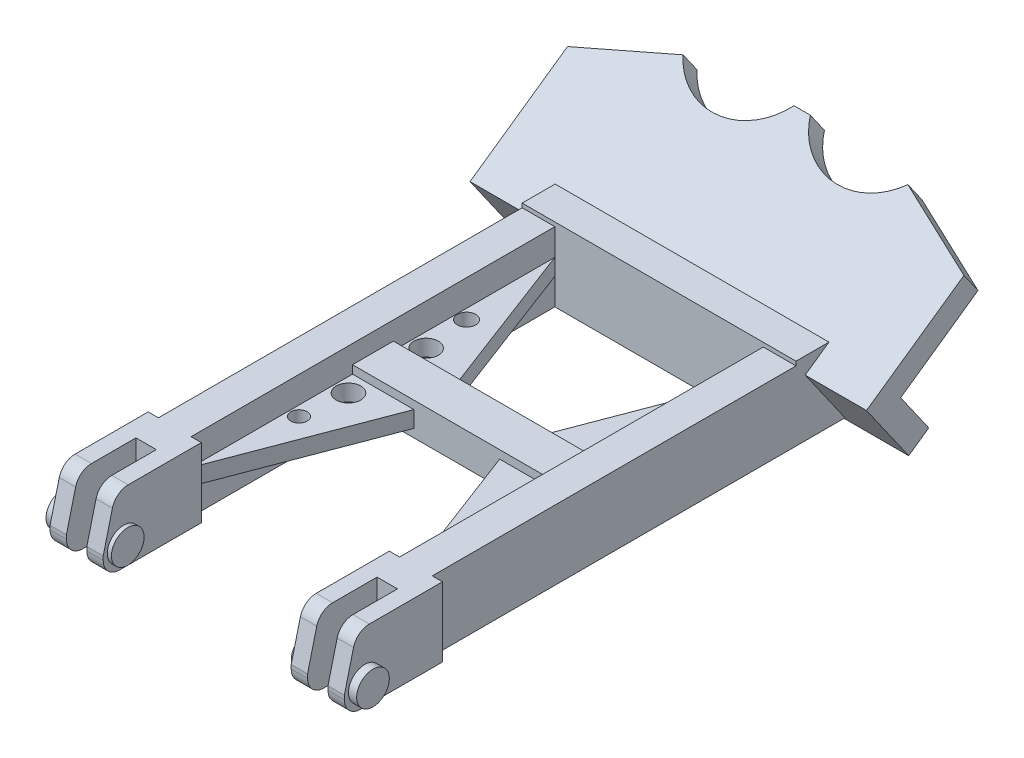
SolidWorks part; units mm, degrees
ref_plane "Front Plane" through (0, 0, 0) normal (0, 0, 1) x (1, 0, 0)
ref_plane "Top Plane" through (0, 0, 0) normal (0, 1, 0) x (1, 0, 0)
ref_plane "Right Plane" through (0, 0, 0) normal (1, 0, 0) x (0, 0, -1)
sketch "Sketch1" plane through (0, 0, 0) normal (0, 1, 0) x (1, 0, 0)
  line L0 (0, 0) -> (0, 8.9) construction
  line L1 (-3.35, 0) -> (-2.55, 0) construction
  line L2 (-3.35, 0) -> (-3.35, 10.1)
  line L3 (-3.35, 10.1) -> (3.35, 10.1)
  line L4 (3.35, 0) -> (3.35, 10.1)
  line L5 (-3.35, 0) -> (-3.6, 0)
  line L6 (-3.6, 0) -> (-3.6, -2.4)
  line L7 (-3.6, -2.4) -> (-2.3, -2.4)
  line L8 (2.55, 0) -> (3.35, 0) construction
  line L9 (-2.55, 0) -> (-2.55, 8.9)
  line L10 (2.55, 0) -> (2.55, 8.9)
  line L11 (-2.55, 8.9) -> (2.55, 8.9)
  line L12 (-2.3, -2.4) -> (-2.3, 0)
  line L13 (-2.3, 0) -> (-2.55, 0)
  line L14 (2.55, 0) -> (2.3, 0)
  line L15 (2.3, 0) -> (2.3, -2.4)
  line L16 (2.3, -2.4) -> (3.6, -2.4)
  line L17 (3.6, -2.4) -> (3.6, 0)
  line L18 (3.6, 0) -> (3.35, 0)
  dimension "D1" = 1.2
  dimension "D2" = 6.7
  dimension "D3" = 0.8
  dimension "D4" = 0.8
  dimension "D5" = 0.25
  dimension "D6" = 2.4
  dimension "D7" = 12.5
extrude "Boss-Extrude1" add sketch "Sketch1" along normal mid plane 1.7
sketch "Sketch3" plane through (0, 0, 0) normal (0, 1, 0) x (1, 0, 0)
  line L0 (-1.05, 3.95) -> (-2.55, 3.95) construction
  line L2 (-2.55, 3.95) -> (-2.55, 0)
  line L3 (-2.55, 0) -> (-2.55, 8.9) construction
  line L4 (-2.55, 0) -> (-1.05, 3.95)
  line L7 (0, 0) -> (0, 13.4734) construction
  line L8 (2.55, 0) -> (1.05, 3.95)
  line L9 (2.55, 3.95) -> (2.55, 0)
  line L10 (1.05, 3.95) -> (2.55, 3.95) construction
  line L11 (-2.55, 4.45) -> (2.55, 4.45) construction
  line L12 (2.55, 8.9) -> (2.55, 0) construction
  line L13 (-1.05, 3.95) -> (1.05, 3.95)
  line L14 (1.05, 4.95) -> (2.55, 4.95) construction
  line L15 (-1.05, 4.95) -> (-2.55, 4.95) construction
  line L16 (-1.05, 4.95) -> (1.05, 4.95)
  line L17 (2.55, 4.95) -> (2.55, 8.9)
  line L18 (2.55, 8.9) -> (1.05, 4.95)
  line L19 (-2.55, 8.9) -> (-1.05, 4.95)
  line L20 (-2.55, 4.95) -> (-2.55, 8.9)
  line L21 (2.55, 4.95) -> (2.55, 3.95)
  line L22 (-2.55, 4.95) -> (-2.55, 3.95)
  line L23 (-2.2, 5.4) -> (-2.31, 6.5) construction
  line L24 (-2.2, 3.5) -> (-2.31, 2.4) construction
  circle A0 centre (-2.2, 3.5) radius 0.3
  circle A1 centre (2.2, 3.5) radius 0.3
  circle A2 centre (-2.31, 2.4) radius 0.2
  circle A3 centre (-2.31, 6.5) radius 0.225
  circle A4 centre (2.2, 5.4) radius 0.3
  circle A5 centre (-2.2, 5.4) radius 0.3
  circle A7 centre (2.31, 2.4) radius 0.2
  circle A9 centre (2.31, 6.5) radius 0.225
  dimension "D1" = 0.6
  dimension "D6" = 0.4
  dimension "D9" = 0.45
  dimension "D2" = 1
  dimension "D3" = 0.35
  dimension "D4" = 2.1
  dimension "D5" = 0.45
  dimension "D7" = 1.1
  dimension "D10" = 1.1
extrude "Boss-Extrude2" add sketch "Sketch3" along normal mid plane 0.4
fillet "Fillet1" radius 0.4 2 edges at (2.95, -0.85, 2.4) (-2.95, -0.85, 2.4)
chamfer "Chamfer1" distance 1.2 distance2 0.3 2 edges at (2.95, 0.85, 2.4) (-2.95, 0.85, 2.4) first distance on face at (2.95, 0.2, 2.4) first distance on face at (-2.95, 0.2, 2.4)
fillet "Fillet2" radius 0.4 2 edges at (2.95, 0.85, 2.1) (-2.95, 0.85, 2.1)
sketch "Sketch7" plane through (-3.6, 0, 0) normal (-1, 0, 0) x (0, 0, 1)
  line L0 (2.4, -0.35) -> (2.4, -0.45) construction
  line L2 (0, -0.85) -> (2, -0.85) construction
  circle A0 centre (1.9, -0.35) radius 0.5 construction
  circle A1 centre (1.9, -0.35) radius 0.4
  dimension "D1" = 1
  dimension "D2" = 0.8
extrude "Boss-Extrude4" add sketch "Sketch7" along normal blind 0.2 and the other way blind 1.4
sketch "Sketch8" plane through (3.6, 0, 0) normal (1, 0, 0) x (0, 0, -1)
  circle A1 centre (-1.9, -0.35) radius 0.4
  circle A2 centre (-1.9, -0.35) radius 0.4
  dimension "D1" = 0
extrude "Boss-Extrude5" add sketch "Sketch8" along normal blind 0.2 and the other way blind 1.4
sketch "Sketch6" plane through (0, 0.85, 0) normal (0, 1, 0) x (1, 0, 0)
  line L0 (-2.3, -2.4) -> (-3.6, -2.4) construction
  line L1 (-3.2, -0.7) -> (-2.7, -0.7)
  line L2 (-3.2, -0.7) -> (-3.2, -2.4)
  line L3 (-3.2, -2.4) -> (-2.7, -2.4)
  line L4 (-2.7, -0.7) -> (-2.7, -2.4)
  line L6 (2.7, -0.7) -> (2.7, -2.4)
  line L7 (3.2, -2.4) -> (2.7, -2.4)
  line L8 (3.2, -0.7) -> (3.2, -2.4)
  line L9 (3.2, -0.7) -> (2.7, -0.7)
  line L10 (-3.35, 0) -> (-3.6, 0) construction
  line L11 (-3.6, 0) -> (-3.6, -1.7877) construction
  line L12 (-2.3, -1.7877) -> (-2.3, 0) construction
  line L13 (0, 0) -> (0, 1.2086) construction
  dimension "D1" = 0.7
  dimension "D2" = 0.4
  dimension "D3" = 0.4
extrude "Cut-Extrude1" cut sketch "Sketch6" against normal through all
sketch "Sketch11" plane through (0, 0.2, 0) normal (0, 1, 0) x (1, 0, 0)
  line L0 (-2.55, 0) -> (-2.55, 8.9) construction
  line L1 (-2.55, 4.95) -> (2.55, 4.95)
  line L2 (-2.55, 4.95) -> (-2.55, 3.95)
  line L3 (-2.55, 3.95) -> (2.55, 3.95)
  line L4 (2.55, 4.95) -> (2.55, 3.95)
  line L5 (2.55, 8.9) -> (2.55, 0) construction
  line L6 (1.05, 4.95) -> (-1.05, 4.95) construction
  line L7 (-1.05, 3.95) -> (1.05, 3.95) construction
extrude "Boss-Extrude8" add sketch "Sketch11" along normal blind 0.2 and the other way blind 0.6
sketch "Sketch12" plane through (0, 0, 0) normal (1, 0, 0) x (0, 0, -1)
  line L0 (9.1249, 0.5426) -> (10.1574, -0.9319)
  line L1 (9.1249, 0.5426) -> (12.4015, 2.8369)
  line L2 (10.1574, -0.9319) -> (10.6488, -0.5878)
  line L3 (10.6488, -0.5878) -> (9.9606, 0.3952)
  line L4 (9.9606, 0.3952) -> (12.7457, 2.3454)
  line L5 (12.7457, 2.3454) -> (12.4015, 2.8369)
  line L6 (0, -0.85) -> (10.1, -0.85) construction
  dimension "D1" = 55
  dimension "D2" = 0.6
  dimension "D3" = 0.6
  dimension "D4" = 4
  dimension "D5" = 1.8
  dimension "D6" = 0.1
extrude "Boss-Extrude9" add sketch "Sketch12" along normal mid plane 9.7
sketch "Sketch13" plane through (3.35, 0, 0) normal (1, 0, 0) x (0, 0, -1)
  line L3 (9.9606, 0.3952) -> (10.1, 0.1961)
  line L4 (10.1, 0.1961) -> (10.1, 0.4929)
  line L5 (10.1, 0.4929) -> (9.9606, 0.3952)
  line L6 (9.9606, 0.3952) -> (10.1, 0.1961)
  line L7 (10.1, 0.1961) -> (10.1, 0.4929)
  line L8 (10.1, 0.4929) -> (9.9606, 0.3952)
  dimension "D1" = 0
extrude "Cut-Extrude2" cut sketch "Sketch13" against normal blind 9.7
sketch "Sketch16" plane through (0, 0, 0) normal (-1, 0, 0) x (0, 0, 1)
  line L0 (-9.9606, 0.3952) -> (-12.7457, 2.3454) construction
  line L1 (-10.6488, -0.5878) -> (-9.9606, 0.3952) construction
  line L2 (-9.9606, 0.3952) -> (-12.1723, 1.9439)
  line L3 (-10.6488, -0.5878) -> (-9.9606, 0.3952)
  line L4 (-10.6488, -0.5878) -> (-12.1723, 1.9439)
  line L5 (-12.7457, 2.3454) -> (-12.4015, 2.8369) construction
  line L6 (-10.1793, 0.5362) -> (-10.8346, 0.995) construction
  circle A0 centre (-10.3227, 0.3314) radius 0.25
  circle A1 centre (-10.9493, 0.8312) radius 0.2
  dimension "D3" = 0.5
  dimension "D4" = 0.4
  dimension "D1" = 0.7
  dimension "D2" = 0.01
  dimension "D5" = 0.26
  dimension "D6" = 0.8
extrude "Boss-Extrude11" add sketch "Sketch16" along normal blind 0.4 from offset 0.7
sketch "Sketch17" plane through (0, 0, 0) normal (1, 0, 0) x (0, 0, -1)
  line L3 (12.1723, 1.9439) -> (9.9606, 0.3952)
  line L4 (10.6488, -0.5878) -> (12.1723, 1.9439)
  line L5 (9.9606, 0.3952) -> (10.6488, -0.5878)
  line L6 (12.1723, 1.9439) -> (9.9606, 0.3952)
  line L7 (10.6488, -0.5878) -> (12.1723, 1.9439)
  line L8 (9.9606, 0.3952) -> (10.6488, -0.5878)
  circle A1 centre (10.9493, 0.8312) radius 0.2
  circle A2 centre (10.9493, 0.8312) radius 0.2
  circle A3 centre (10.3227, 0.3314) radius 0.25
  circle A4 centre (10.3227, 0.3314) radius 0.25
  dimension "D1" = 0
  dimension "D2" = 0
  dimension "D3" = 0
extrude "Boss-Extrude12" add sketch "Sketch17" along normal blind 0.4 from offset 0.7
sketch "Sketch14" plane through (0, -4.4147, -3.0912) normal (0, -0.8192, -0.5736) x (-1, 0, 0)
  line L0 (-4.85, 10.6963) -> (-2.75, 11.5859)
  line L1 (-0.2, 11.7859) -> (0.2, 11.7859)
  line L2 (-4.85, 11.7859) -> (4.85, 11.7859) construction
  line L3 (-4.85, 8.3859) -> (-4.85, 11.7859) construction
  line L4 (4.85, 10.6963) -> (4.85, 12.7859)
  line L5 (0, 0) -> (0, 11.5926) construction
  line L6 (4.85, 10.6963) -> (2.75, 11.5859)
  line L7 (-4.85, 10.6963) -> (-4.85, 12.7859)
  line L8 (-4.85, 12.7859) -> (4.85, 12.7859)
  arc A0 (-2.75, 11.5859) -> (-0.2, 11.7859) centre (-1.5363, 12.4673) ccw
  arc A1 (2.75, 11.5859) -> (0.2, 11.7859) centre (1.5363, 12.4673) cw
  point P18 (0, 12.7859)
  dimension "D5" = 1.5
  dimension "D1" = 1
  dimension "D2" = 5.5
  dimension "D3" = 1.0896
  dimension "D4" = 0.4
  dimension "D6" = 0.2
extrude "Cut-Extrude3" cut sketch "Sketch14" against normal blind 1 and the other way blind 0.4
sketch "Sketch18" plane through (0, 0.85, 0) normal (0, 1, 0) x (1, 0, 0)
  line L0 (-3.35, 9.564) -> (-3.35, 0) construction
  line L1 (-3.35, 8.9) -> (3.35, 8.9)
  line L2 (-3.35, 8.9) -> (-3.35, 9.9)
  line L3 (-3.35, 9.9) -> (3.35, 9.9)
  line L4 (3.35, 8.9) -> (3.35, 9.9)
  line L5 (-2.55, 8.9) -> (2.55, 8.9) construction
  dimension "D1" = 1
extrude "Boss-Extrude13" add sketch "Sketch18" along normal blind 0.1
scale "Scale1" scale about origin uniform scaling yes scale factor 2
sketch "Sketch19" plane through (-7.2, 0, 0) normal (-1, 0, 0) x (0, 0, 1)
  line L0 (0, -1.7) -> (4, -1.7) construction
  line L1 (4.8, -0.7) -> (4.3515, 1.094) construction
  line L2 (0, 1.7) -> (3.5754, 1.7) construction
  circle A0 centre (2.8727, 0) radius 1.7
ref_axis "Axis1" through (-7.2, 0, 2.8727) along (-1, 0, 0)
